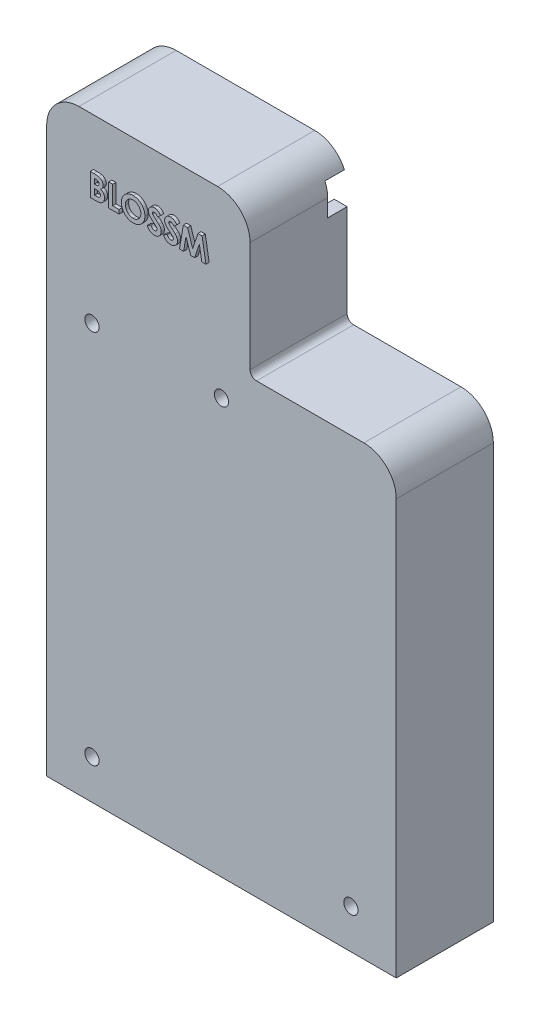
SolidWorks part; units mm, degrees
other "Markup1"
sketch "Sketch13" plane through (0.4487, 1125.5894, 1303.4729) normal (-0.633, 0.4523, -0.6282) x (-0.2198, -0.8831, -0.4145)
ref_plane "Front Plane" through (0, 0, 0) normal (0, 0, 1) x (1, 0, 0)
ref_plane "Top Plane" through (0, 0, 0) normal (0, 1, 0) x (1, 0, 0)
ref_plane "Right Plane" through (0, 0, 0) normal (1, 0, 0) x (0, 0, -1)
sketch "Sketch3" plane through (0, 0, 1303.4729) normal (0, 0, 1) x (1, 0, 0)
  line L0 (787.6501, 933.5894) -> (787.6501, 1120.5894) construction
  line L1 (787.6501, 1035.4965) -> (787.6501, 1120.5894)
  line L2 (837.6501, 1097.5894) -> (837.6501, 933.5894) construction
  line L3 (818.0661, 1100.5894) -> (834.6501, 1100.5894) construction
  line L4 (815.0661, 1120.5894) -> (815.0661, 1103.5894) construction
  line L5 (790.6501, 1123.5894) -> (812.0661, 1123.5894) construction
  line L6 (837.6501, 1097.5894) -> (837.6501, 1035.4965)
  line L7 (818.0661, 1100.5894) -> (834.6501, 1100.5894)
  line L8 (815.0661, 1120.5894) -> (815.0661, 1103.5894)
  line L9 (790.6501, 1123.5894) -> (812.0661, 1123.5894)
  line L10 (787.6501, 1035.4965) -> (837.6501, 1035.4965) construction
  line L11 (787.6501, 1035.4965) -> (837.6501, 1035.4965)
  line L12 (839.6501, 1097.5898) -> (839.6501, 1033.4965)
  line L13 (785.6501, 1033.4965) -> (839.6501, 1033.4965)
  line L14 (785.6501, 1033.4965) -> (785.6501, 1120.5898)
  line L15 (790.6497, 1125.5894) -> (812.0665, 1125.5894)
  line L16 (817.0661, 1120.5898) -> (817.0661, 1103.5898)
  line L17 (818.0665, 1102.5894) -> (834.6505, 1102.5894)
  arc A0 (837.6501, 1097.5894) -> (834.6501, 1100.5894) centre (834.649, 1097.5883) ccw construction
  arc A1 (815.0661, 1103.5894) -> (818.0661, 1100.5894) centre (818.0672, 1103.5905) ccw construction
  arc A2 (815.0661, 1120.5894) -> (812.0661, 1123.5894) centre (812.065, 1120.5883) ccw construction
  arc A3 (790.6501, 1123.5894) -> (787.6501, 1120.5894) centre (790.6512, 1120.5883) ccw construction
  arc A4 (837.6501, 1097.5894) -> (834.6501, 1100.5894) centre (834.649, 1097.5883) ccw
  arc A5 (815.0661, 1103.5894) -> (818.0661, 1100.5894) centre (818.0672, 1103.5905) ccw
  arc A6 (815.0661, 1120.5894) -> (812.0661, 1123.5894) centre (812.065, 1120.5883) ccw
  arc A7 (790.6501, 1123.5894) -> (787.6501, 1120.5894) centre (790.6512, 1120.5883) ccw
  arc A8 (790.6497, 1125.5894) -> (785.6501, 1120.5898) centre (790.6512, 1120.5883) ccw
  arc A9 (817.0661, 1120.5898) -> (812.0665, 1125.5894) centre (812.065, 1120.5883) ccw
  arc A10 (817.0661, 1103.5898) -> (818.0665, 1102.5894) centre (818.0672, 1103.5905) ccw
  arc A11 (839.6501, 1097.5898) -> (834.6505, 1102.5894) centre (834.649, 1097.5883) ccw
  dimension "D1" = 2
sketch "Sketch6" plane through (0, 0, 1303.4729) normal (0, 0, 1) x (1, 0, 0)
  line L0 (787.6501, 1035.4965) -> (837.6501, 1035.4965) construction
  line L1 (837.6501, 1097.5894) -> (837.6501, 1035.4965) construction
  line L2 (818.0661, 1100.5894) -> (834.6501, 1100.5894) construction
  line L3 (815.0661, 1120.5894) -> (815.0661, 1103.5894) construction
  line L4 (790.6501, 1123.5894) -> (812.0661, 1123.5894) construction
  line L5 (787.6501, 1035.4965) -> (787.6501, 1120.5894) construction
  line L6 (787.6501, 1035.4965) -> (837.6501, 1035.4965)
  line L7 (837.6501, 1097.5894) -> (837.6501, 1035.4965)
  line L8 (818.0661, 1100.5894) -> (834.6501, 1100.5894)
  line L9 (815.0661, 1120.5894) -> (815.0661, 1103.5894)
  line L10 (790.6501, 1123.5894) -> (812.0661, 1123.5894)
  line L11 (787.6501, 1035.4965) -> (787.6501, 1120.5894)
  arc A0 (837.6501, 1097.5894) -> (834.6501, 1100.5894) centre (834.649, 1097.5883) ccw construction
  arc A1 (815.0661, 1103.5894) -> (818.0661, 1100.5894) centre (818.0672, 1103.5905) ccw construction
  arc A2 (815.0661, 1120.5894) -> (812.0661, 1123.5894) centre (812.065, 1120.5883) ccw construction
  arc A3 (790.6501, 1123.5894) -> (787.6501, 1120.5894) centre (790.6512, 1120.5883) ccw construction
  arc A4 (837.6501, 1097.5894) -> (834.6501, 1100.5894) centre (834.649, 1097.5883) ccw
  arc A5 (815.0661, 1103.5894) -> (818.0661, 1100.5894) centre (818.0672, 1103.5905) ccw
  arc A6 (815.0661, 1120.5894) -> (812.0661, 1123.5894) centre (812.065, 1120.5883) ccw
  arc A7 (790.6501, 1123.5894) -> (787.6501, 1120.5894) centre (790.6512, 1120.5883) ccw
extrude "Boss-Extrude1" add sketch "Sketch3" along normal blind 15
extrude "Boss-Extrude2" add sketch "Sketch6" along normal blind 15
extrude "Cut-Extrude1" cut sketch "Sketch6<2>" along normal blind 14
sketch "Sketch6<2>" plane through (0, 0, 1303.4729) normal (0, 0, 1) x (1, 0, 0) same geometry as "Sketch6"
sketch "Sketch8" plane through (0, 0, 1303.4729) normal (0, 0, 1) x (1, 0, 0)
  line L10 (791.5267, 1122.6166) -> (784.8275, 1122.6166)
  line L11 (791.5267, 1122.6166) -> (791.5267, 1117.8952)
  line L12 (791.5267, 1117.8952) -> (784.8275, 1117.8952)
  line L13 (784.8275, 1122.6166) -> (784.8275, 1117.8952)
  line L14 (809.8444, 1122.6166) -> (818.0733, 1122.6166)
  line L15 (809.8444, 1122.6166) -> (809.8444, 1117.8952)
  line L16 (809.8444, 1117.8952) -> (818.0733, 1117.8952)
  line L17 (818.0733, 1122.6166) -> (818.0733, 1117.8952)
extrude "Cut-Extrude7" cut sketch "Sketch8" along normal blind 3
sketch "Sketch10" plane through (0, 0, 1303.4729) normal (0, 0, 1) x (1, 0, 0)
  circle A0 centre (832.6501, 1039.5894) radius 1.1 construction
  circle A1 centre (792.6501, 1039.5894) radius 1.1 construction
  circle A2 centre (792.6501, 1097.5894) radius 1.1 construction
  circle A3 centre (812.6501, 1097.5894) radius 1.1 construction
  circle A4 centre (832.6501, 1039.5894) radius 1.1
  circle A5 centre (792.6501, 1039.5894) radius 1.1
  circle A6 centre (792.6501, 1097.5894) radius 1.1
  circle A7 centre (812.6501, 1097.5894) radius 1.1
  circle A8 centre (792.6501, 1039.5894) radius 2.1
  circle A9 centre (832.6501, 1039.5894) radius 2.1
  circle A10 centre (812.6501, 1097.5894) radius 2.1
  circle A11 centre (792.6501, 1097.5894) radius 2.1
  dimension "D1" = 1
extrude "Boss-Extrude4" add sketch "Sketch10" along normal up to next
sketch "Sketch11" plane through (0, 0, 1303.4729) normal (0, 0, 1) x (1, 0, 0)
  circle A0 centre (792.6501, 1097.5894) radius 1.1 construction
  circle A1 centre (792.6501, 1097.5894) radius 1.1
  circle A2 centre (812.6501, 1097.5894) radius 1.1 construction
  circle A3 centre (812.6501, 1097.5894) radius 1.1
  circle A4 centre (792.6501, 1039.5894) radius 1.1 construction
  circle A5 centre (792.6501, 1039.5894) radius 1.1
  circle A6 centre (832.6501, 1039.5894) radius 1.1 construction
  circle A7 centre (832.6501, 1039.5894) radius 1.1
extrude "Cut-Extrude8" cut sketch "Sketch11" along normal up to surface (15 mm away) up to face at (814.0994, 1096.8608, 1318.4729)
sketch "Sketch12" plane through (0, 0, 1318.4729) normal (0, 0, 1) x (1, 0, 0)
  text T0 "BLOSSM"
  text T1 "<b>BLOSSM</b>"
extrude "Boss-Extrude5" add sketch "Sketch12" along normal blind 0.5
delete or keep bodies "Body-Delete/Keep 1" type delete bodies bodies 113 111 114 115 116 112
